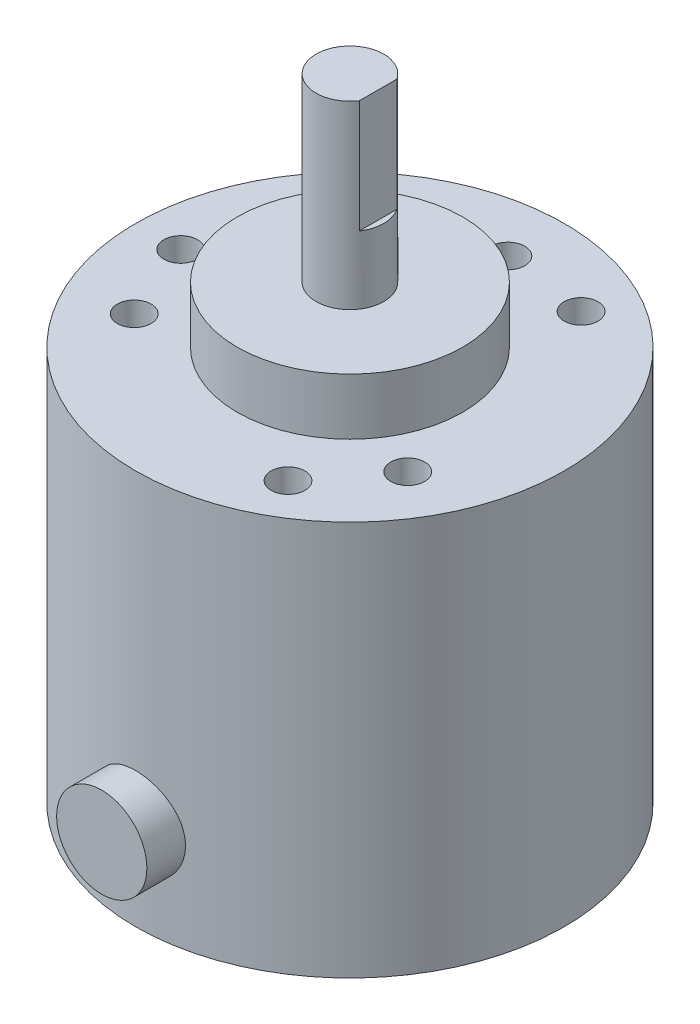
SolidWorks part; units mm, degrees
ref_plane "Front Plane" through (0, 0, 0) normal (0, 0, 1) x (1, 0, 0)
ref_plane "Top Plane" through (0, 0, 0) normal (0, 1, 0) x (1, 0, 0)
ref_plane "Right Plane" through (0, 0, 0) normal (1, 0, 0) x (0, 0, -1)
sketch "Sketch2" plane through (0, 0, 0) normal (0, 1, 0) x (1, 0, 0)
  circle A0 centre (0, 0) radius 19
  dimension "D1" = 38
extrude "Boss-Extrude2" add sketch "Sketch2" against normal blind 35 contours A0
sketch "Sketch4" plane through (0, 0, 0) normal (0, 1, 0) x (1, 0, 0)
  circle A0 centre (0, 0) radius 10
  dimension "D1" = 20
extrude "Boss-Extrude3" add sketch "Sketch4" along normal blind 5
sketch "Sketch5" plane through (0, 5, 0) normal (0, 1, 0) x (1, 0, 0)
  circle A0 centre (0, 0) radius 3
  dimension "D1" = 6
extrude "Boss-Extrude4" add sketch "Sketch5" along normal blind 16
sketch "Sketch8" plane through (0, 21, 0) normal (0, 1, 0) x (1, 0, 0)
  line L5 (3, -3.1414) -> (2.5, -3.1414)
  line L6 (3, -3.1414) -> (3, 2.9748)
  line L7 (3, 2.9748) -> (2.5, 2.9748)
  line L8 (2.5, -3.1414) -> (2.5, 2.9748)
  circle A1 centre (0, 0) radius 3 construction
  dimension "D1" = 0.5
extrude "Cut-Extrude2" cut sketch "Sketch8" against normal blind 10
sketch "Sketch10" plane through (0, 0, 0) normal (0, 1, 0) x (1, 0, 0)
  circle A0 centre (0, 0) radius 15 construction
  circle A1 centre (0, 0) radius 14 construction
  circle A2 centre (-15, 0) radius 1.5
  circle A3 centre (0, 14) radius 1.5
  circle A4 centre (7.5, 12.9904) radius 1.5
  circle A5 centre (7.5, -12.9904) radius 1.5
  circle A6 centre (12.1244, -7) radius 1.5
  circle A7 centre (-12.1244, -7) radius 1.5
  circle A8 centre (0, 0) radius 10 construction
  point P4 (-15, 0)
  point P14 (0, 0)
  point P18 (-12.1244, -7)
  point P20 (0, 0)
  point P29 (-16.4737, -0.2796)
  point P31 (-15, 0)
  dimension "D1" = 30
  dimension "D2" = 28
  dimension "D3" = 3
  dimension "D4" = 3
  dimension "D5" = 3
  dimension "D6" = 3
extrude "Cut-Extrude3" cut sketch "Sketch10" against normal blind 7 contours A2 | A7 | A3 | A4 | A6 | A5
sketch "Sketch15" plane through (0, 0, 0) normal (0, 0, 1) x (1, 0, 0)
  circle A0 centre (0, -27) radius 4
  dimension "D2" = 8
extrude "Boss-Extrude5" add sketch "Sketch15" along normal blind 22 contours A0
